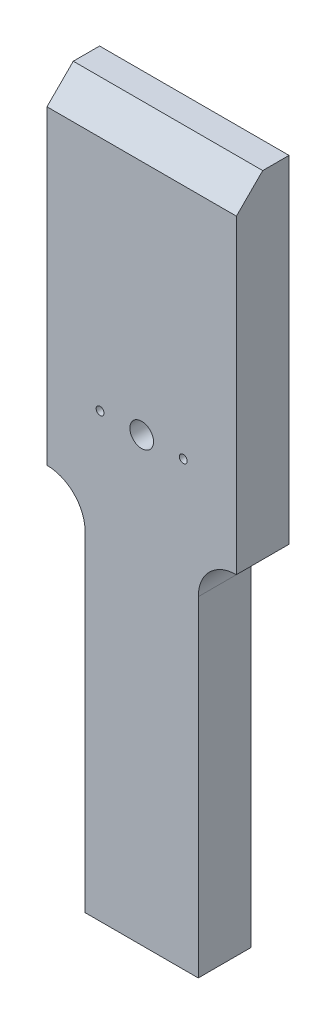
SolidWorks part; units mm, degrees
material "Pine"
ref_plane "Front Plane" through (0, 0, 0) normal (0, 0, 1) x (1, 0, 0)
ref_plane "Top Plane" through (0, 0, 0) normal (0, 1, 0) x (1, 0, 0)
ref_plane "Right Plane" through (0, 0, 0) normal (1, 0, 0) x (0, 0, -1)
sketch "Sketch1" plane through (0, 0, 0) normal (0, 0, 1) x (1, 0, 0)
  line L0 (0, 0) -> (0, -50000) construction
  line L1 (114.3, 203.2) -> (-114.3, 203.2)
  line L2 (114.3, 203.2) -> (114.3, -203.2)
  line L3 (114.3, -203.2) -> (-114.3, -203.2)
  line L4 (-114.3, 203.2) -> (-114.3, -203.2)
  line L5 (114.3, 203.2) -> (-114.3, -203.2) construction
  line L6 (114.3, -203.2) -> (-114.3, 203.2) construction
  line L7 (-68.2625, -647.7) -> (68.2625, -647.7)
  line L8 (-68.2625, -647.7) -> (-68.2625, -203.2)
  line L9 (-68.2625, -203.2) -> (68.2625, -203.2)
  line L10 (68.2625, -647.7) -> (68.2625, -203.2)
  line L11 (-68.2625, -647.7) -> (68.2625, -203.2) construction
  line L12 (-68.2625, -203.2) -> (68.2625, -647.7) construction
  line L14 (-50.1741, -114.3) -> (50.1741, -114.3) construction
  circle A3 centre (0, -114.3) radius 14.2875 construction
  circle A4 centre (0, -114.3) radius 14.2875
  circle A5 centre (-50.1741, -114.3) radius 4.7625
  circle A6 centre (50.1741, -114.3) radius 4.7625
  point P0 (0, 0)
  point P6 (0, -425.45)
  point P25 (0, -114.3)
  dimension "D8" = 9.525
  dimension "D1" = 136.525
  dimension "D2" = 444.5
  dimension "D3" = 406.4
  dimension "D4" = 228.6
extrude "Boss-Extrude1" add sketch "Sketch1" along normal blind 63.5 contours L7 L10 L3 L8 | L4 L3 L2 L1 | A4 | A5 | A6 region at (0, -425.45, 0)
sketch "Sketch2" plane through (0, 0, 0) normal (0, 0, -1) x (-1, 0, 0)
  line L0 (0, 0) -> (0, -50000) construction
  line L2 (-19.05, -217.4875) -> (19.05, -217.4875)
  line L3 (-19.05, -217.4875) -> (-19.05, -712.7875)
  line L4 (-19.05, -712.7875) -> (19.05, -712.7875)
  line L5 (19.05, -217.4875) -> (19.05, -712.7875)
  line L6 (-19.05, -217.4875) -> (19.05, -712.7875) construction
  line L7 (-19.05, -712.7875) -> (19.05, -217.4875) construction
  circle A2 centre (0, -114.3) radius 103.1875
  circle A3 centre (0, -114.3) radius 103.1875 construction
  point P3 (0, -465.1375)
  dimension "D1" = 38.1
  dimension "D2" = 495.3
  dimension "D3" = 88.9
extrude "Cut-Extrude1" cut sketch "Sketch2" against normal blind 36.5125
sketch "Sketch3" plane through (-114.3, 0, 0) normal (-1, 0, 0) x (0, 0, 1)
  line L0 (0, 203.2) -> (0, -203.2) construction
  line L5 (0, -647.7) -> (36.5125, -647.7)
  line L6 (0, -217.4875) -> (0, -647.7)
  line L7 (0, -647.7) -> (36.5125, -647.7)
  line L8 (36.5125, -647.7) -> (36.5125, -217.4875)
  line L9 (36.5125, -217.4875) -> (0, -217.4875)
  line L10 (0, -217.4875) -> (0, -647.7)
  line L12 (36.5125, -647.7) -> (36.5125, -217.4875)
  line L13 (36.5125, -217.4875) -> (0, -217.4875)
  circle A0 centre (19.05, -239.7125) radius 4.7625
  dimension "D4" = 9.525
  dimension "D1" = 19.05
  dimension "D2" = 0
  dimension "D3" = 22.225
extrude "Cut-Extrude2" cut sketch "Sketch3" against normal through all contours A0 region at (-114.3, -239.7125, 19.05)
fillet "Fillet1" radius 46.0375 2 edges at (68.2625, -203.2, 31.75) (-68.2625, -203.2, 31.75)
chamfer "Chamfer1" distance 31.75 angle 45 1 edges at (0, 203.2, 63.5)
